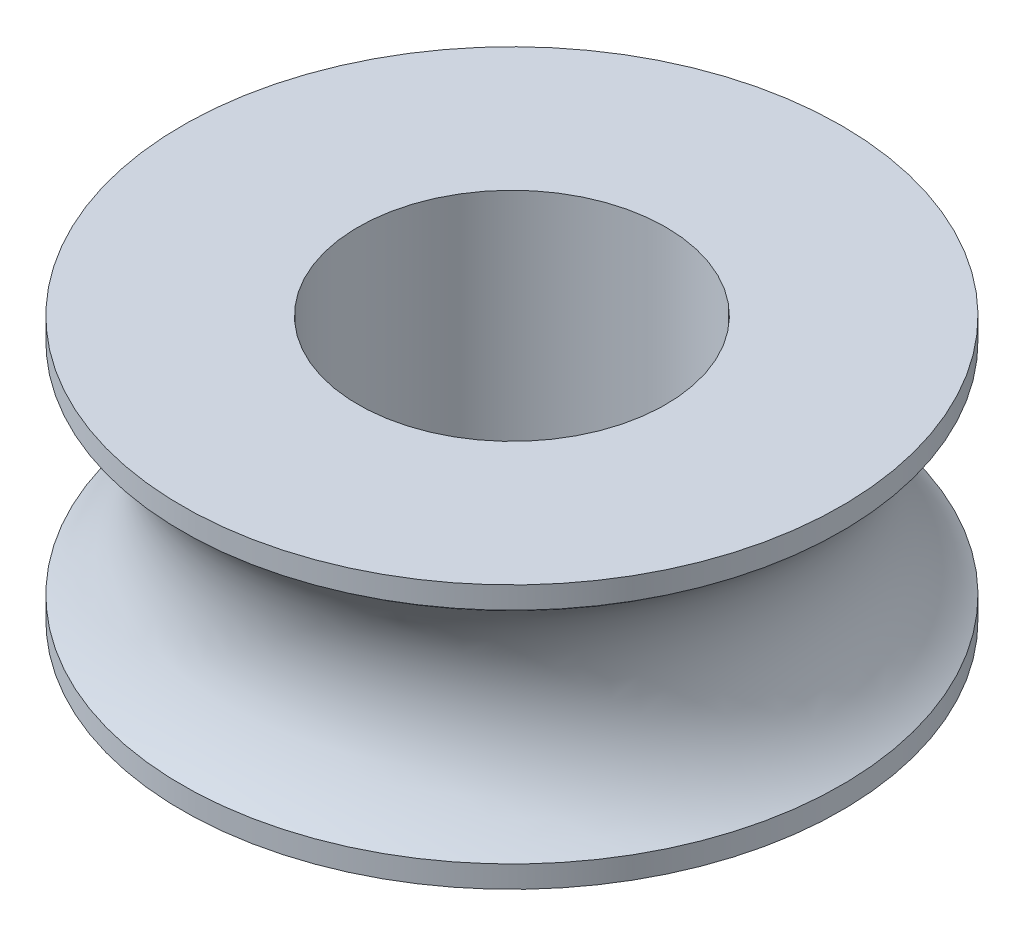
SolidWorks part; units mm, degrees
ref_plane "Ebene vorne" through (0, 0, 0) normal (0, 0, 1) x (1, 0, 0)
ref_plane "Ebene oben" through (0, 0, 0) normal (0, 1, 0) x (1, 0, 0)
ref_plane "Ebene rechts" through (0, 0, 0) normal (1, 0, 0) x (0, 0, -1)
sketch "Sketch1" plane through (0, 0, 0) normal (0, 0, 1) x (1, 0, 0)
  line L0 (0, -6.6295) -> (0, 11.8219) construction
  line L1 (-2.5, 0) -> (-7.5, 0)
  line L2 (-7.5, 0) -> (-7.5, 0.5)
  line L3 (-7.5, 6) -> (-3.5, 6)
  line L4 (-3.5, 6) -> (-3.5, 1)
  line L5 (-3.5, 1) -> (-2.5, 1)
  line L6 (-2.5, 1) -> (-2.5, 0)
  line L7 (-7.5, 5.5) -> (-7.5, 6)
  line L8 (-9.5365, 3) -> (-4.4754, 3) construction
  arc A0 (-7.5, 0.5) -> (-7.5, 5.5) centre (-9.1583, 3) ccw
  dimension "D6" = 3
  dimension "D1" = 7
  dimension "D2" = 5
  dimension "D3" = 1
  dimension "D4" = 5
  dimension "D5" = 15
  dimension "D7" = 5
revolve "Revolve1" add sketch "Sketch1" angle 360 about L0
